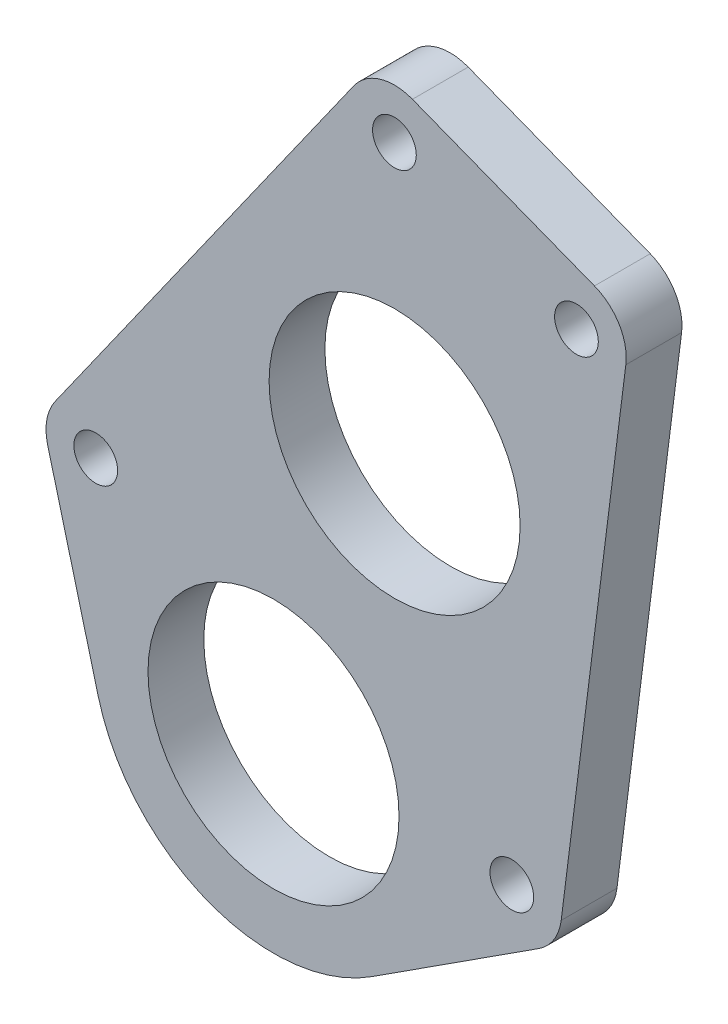
SolidWorks part; units mm, degrees
material "6061-T6 (SS)"
ref_plane "Front Plane" through (0, 0, 0) normal (0, 0, 1) x (1, 0, 0)
ref_plane "Top Plane" through (0, 0, 0) normal (0, 1, 0) x (1, 0, 0)
ref_plane "Right Plane" through (0, 0, 0) normal (1, 0, 0) x (0, 0, -1)
sketch "Sketch1" plane through (0, 0, 0) normal (0, 0, 1) x (1, 0, 0)
  line L0 (13.7841, 35.5191) -> (0, 0) construction
  line L1 (-20.2334, 18.0692) -> (27.1254, -0.3096) construction
  line L2 (13.7841, 35.5191) -> (24.1222, 62.1585) construction
  line L3 (0, 0) -> (23.1556, 0) construction
  line L4 (-25.7114, 16.6288) -> (-19.9591, -5.2481)
  line L5 (11.194, -17.3378) -> (30.1978, -5.0682)
  line L8 (13.7624, 66.1788) -> (34.4819, 58.1381) construction
  line L9 (-24.8592, 21.3379) -> (9.1366, 69.4476)
  line L10 (32.7453, -1.017) -> (40.1018, 57.4308)
  line L11 (15.8117, 71.4594) -> (36.5311, 63.4186)
  circle A0 centre (0, 0) radius 14.2875
  circle A1 centre (13.7841, 35.5191) radius 14.2875
  circle A2 centre (-20.2334, 18.0692) radius 2.4892
  circle A3 centre (27.1254, -0.3096) radius 2.4892
  arc A5 (-19.9591, -5.2481) -> (11.194, -17.3378) centre (0, 0) ccw
  circle A9 centre (0, 0) radius 20.6375 construction
  circle A10 centre (34.4819, 58.1381) radius 2.4892
  circle A11 centre (13.7624, 66.1788) radius 2.4892
  arc A12 (-24.8592, 21.3379) -> (-25.7114, 16.6288) centre (-20.2334, 18.0692) ccw
  arc A13 (30.1978, -5.0682) -> (32.7453, -1.017) centre (27.1254, -0.3096) ccw
  arc A14 (40.1018, 57.4308) -> (36.5311, 63.4186) centre (34.4819, 58.1381) ccw
  arc A15 (15.8117, 71.4594) -> (9.1366, 69.4476) centre (13.7624, 66.1788) ccw
  circle A16 centre (-20.2334, 18.0692) radius 5.6642 construction
  circle A17 centre (27.1254, -0.3096) radius 5.6642 construction
  circle A18 centre (34.4819, 58.1381) radius 5.6642 construction
  circle A19 centre (13.7624, 66.1788) radius 5.6642 construction
  point P12 (29.5346, 9.6163)
  point P17 (24.1222, 62.1585)
  point P32 (3.446, 8.8798)
  point P40 (28.2306, 2.5382)
  dimension "D1" = 28.575
  dimension "D3" = 4.9784
  dimension "D2" = 38.1
  dimension "D4" = 28.575
  dimension "D5" = 50.8
  dimension "D6" = 68.79
  dimension "D8" = 22.225
  dimension "D10" = 9.525
  dimension "D7" = 6.35
  dimension "D9" = 3.175
extrude "Boss-Extrude1" add sketch "Sketch1" along normal mid plane 6.35
equation "\"D2@Sketch1\"=60/40"
